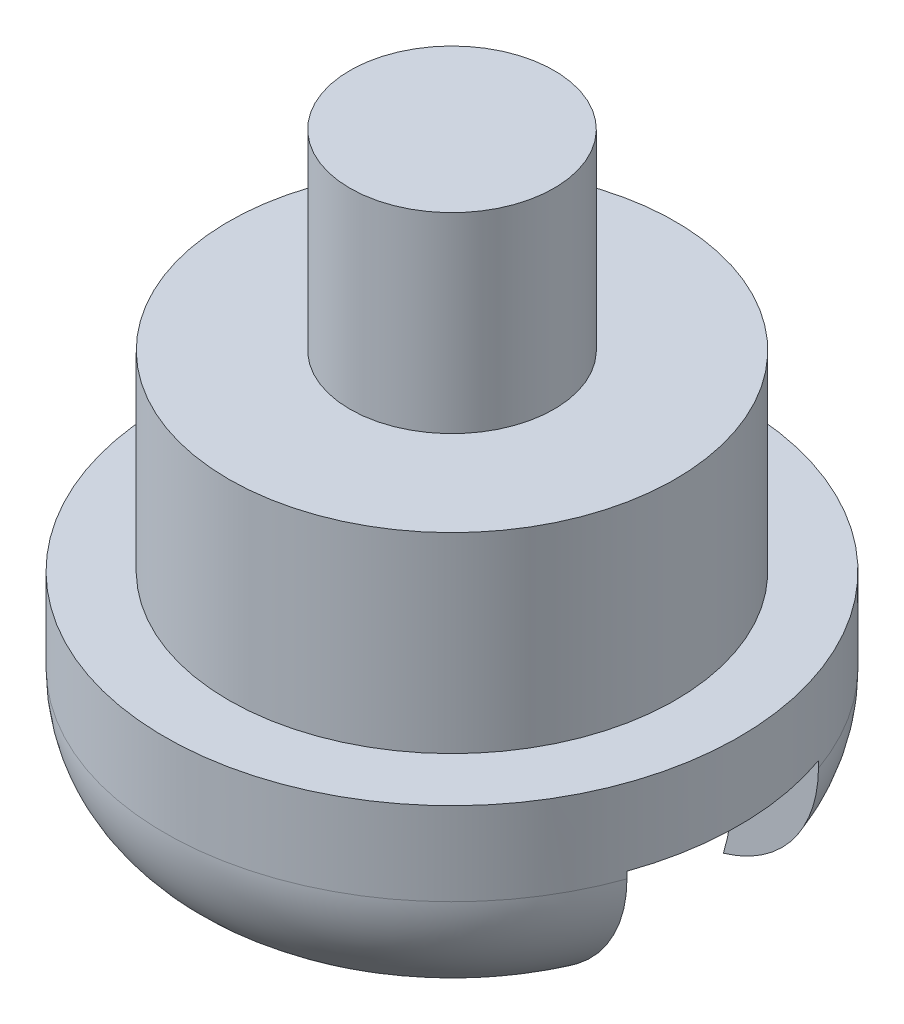
SolidWorks part; units mm, degrees
ref_plane "Front Plane" through (0, 0, 0) normal (0, 0, 1) x (1, 0, 0)
ref_plane "Top Plane" through (0, 0, 0) normal (0, 1, 0) x (1, 0, 0)
ref_plane "Right Plane" through (0, 0, 0) normal (1, 0, 0) x (0, 0, -1)
sketch "Sketch1" plane through (0, 0, 0) normal (0, 1, 0) x (1, 0, 0)
  circle A0 centre (0, 0) radius 3.5
  dimension "D1" = 7
extrude "base" add sketch "Sketch1" along normal blind 3
sketch "Sketch2" plane through (0, 3, 0) normal (0, 1, 0) x (1, 0, 0)
  circle A0 centre (0, 0) radius 1.6
  dimension "D1" = 3.2
extrude "peg" add sketch "Sketch2" along normal blind 3
sketch "Sketch5" plane through (0, 0, 0) normal (0, -1, 0) x (1, 0, 0)
  circle A0 centre (0, 0) radius 4.5
  dimension "D1" = 9
extrude "holder" add sketch "Sketch5" along normal blind 3.2
sketch "Sketch6" plane through (0, 0, 0) normal (1, 0, 0) x (0, 0, -1)
  line L0 (0, 6) -> (0, -5.5978) construction
  line L1 (1.6, 6) -> (-1.6, 6) construction
  line L2 (0, 0.9022) -> (0, -5.5978)
  arc A0 (0, -5.5978) -> (0, 0.9022) centre (0, -2.3478) cw
  point P7 (0, 0.9022)
  dimension "D1" = 6.5
revolve "Cut-ball" cut sketch "Sketch6" angle 360 about L0
sketch "Sketch8" plane through (0, -3.2, 0) normal (0, -1, 0) x (1, 0, 0)
  line L1 (-6, 1.5) -> (6, 1.5)
  line L2 (-6, 1.5) -> (-6, -1.5)
  line L3 (-6, -1.5) -> (6, -1.5)
  line L4 (6, 1.5) -> (6, -1.5)
  line L5 (-6, 1.5) -> (6, -1.5) construction
  line L6 (-6, -1.5) -> (6, 1.5) construction
  point P0 (0, 0)
  dimension "D1" = 3
  dimension "D2" = 12
extrude "Cut-slot" cut sketch "Sketch8" against normal blind 2
fillet "Fillet1" radius 2 2 edges at (0, -3.2, -4.5) (0, -3.2, 4.5)
